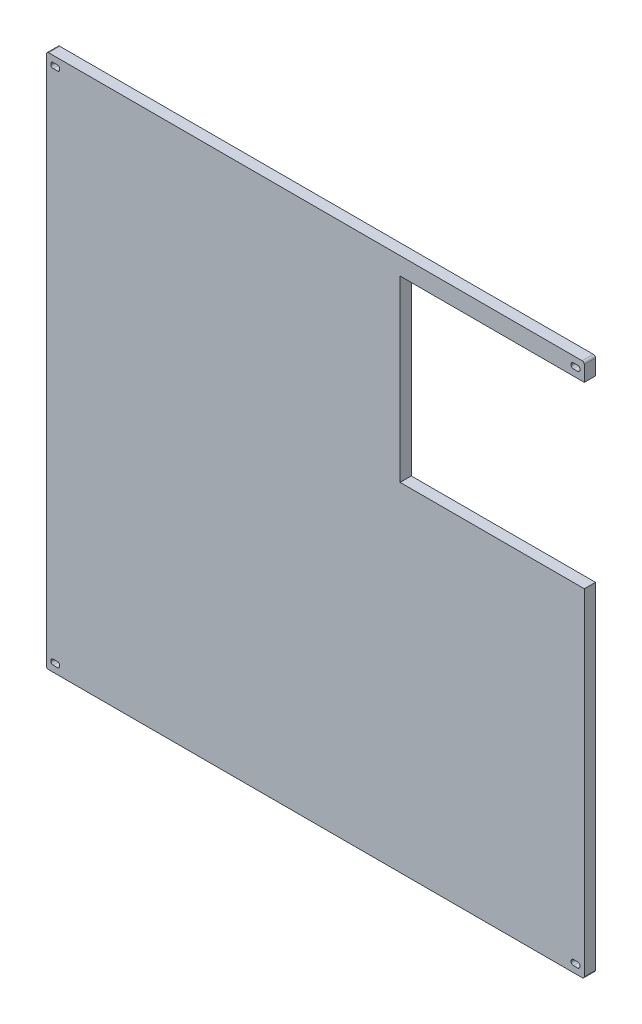
SolidWorks part; units mm, degrees
ref_plane "Front Plane" through (0, 0, 0) normal (0, 0, 1) x (1, 0, 0)
ref_plane "Top Plane" through (0, 0, 0) normal (0, 1, 0) x (1, 0, 0)
ref_plane "Right Plane" through (0, 0, 0) normal (1, 0, 0) x (0, 0, -1)
sketch "Sketch1" plane through (0, 0, 0) normal (0, 0, 1) x (1, 0, 0)
  line L0 (-5, 10.5) -> (-5, 9.5)
  line L1 (0, 0) -> (-611.632, 0)
  line L2 (0, 0) -> (0, 384.2809)
  line L3 (0, 607.568) -> (-611.632, 607.568)
  line L4 (-611.632, 0) -> (-611.632, 607.568)
  line L5 (0, 587.4809) -> (0, 607.568)
  line L6 (0, 587.4809) -> (-209.5191, 587.4809)
  line L8 (0, 384.2809) -> (-209.5191, 384.2809)
  line L9 (-209.5191, 587.4809) -> (-209.5191, 384.2809)
  line L10 (-7.5, 13) -> (-12.5, 13)
  line L11 (-15, 10.5) -> (-15, 9.5)
  line L12 (-7.5, 7) -> (-12.5, 7)
  line L13 (-10, 13) -> (-10, 7) construction
  line L14 (-15, 10) -> (-5, 10) construction
  line L15 (-596.63, 10.5) -> (-596.63, 9.5)
  line L16 (-599.13, 7) -> (-604.13, 7)
  line L17 (-606.63, 10.5) -> (-606.63, 9.5)
  line L18 (-599.13, 13) -> (-604.13, 13)
  line L19 (-596.63, 598.07) -> (-596.63, 597.07)
  line L20 (-599.13, 594.57) -> (-604.13, 594.57)
  line L21 (-606.63, 598.07) -> (-606.63, 597.07)
  line L22 (-599.13, 600.57) -> (-604.13, 600.57)
  line L23 (-5, 598.07) -> (-5, 597.07)
  line L24 (-7.5, 594.57) -> (-12.5, 594.57)
  line L25 (-15, 598.07) -> (-15, 597.07)
  line L26 (-7.5, 600.57) -> (-12.5, 600.57)
  line L27 (-209.5191, 641.3) -> (-209.5191, 384.2809) construction
  arc A0 (-5, 10.5) -> (-7.5, 13) centre (-7.5, 10.5) ccw
  arc A1 (-12.5, 13) -> (-15, 10.5) centre (-12.5, 10.5) ccw
  arc A2 (-5, 9.5) -> (-7.5, 7) centre (-7.5, 9.5) cw
  arc A3 (-15, 9.5) -> (-12.5, 7) centre (-12.5, 9.5) ccw
  arc A4 (-596.63, 9.5) -> (-599.13, 7) centre (-599.13, 9.5) cw
  arc A5 (-606.63, 9.5) -> (-604.13, 7) centre (-604.13, 9.5) ccw
  arc A6 (-604.13, 13) -> (-606.63, 10.5) centre (-604.13, 10.5) ccw
  arc A7 (-596.63, 10.5) -> (-599.13, 13) centre (-599.13, 10.5) ccw
  arc A8 (-596.63, 597.07) -> (-599.13, 594.57) centre (-599.13, 597.07) cw
  arc A9 (-606.63, 597.07) -> (-604.13, 594.57) centre (-604.13, 597.07) ccw
  arc A10 (-604.13, 600.57) -> (-606.63, 598.07) centre (-604.13, 598.07) ccw
  arc A11 (-596.63, 598.07) -> (-599.13, 600.57) centre (-599.13, 598.07) ccw
  arc A12 (-5, 597.07) -> (-7.5, 594.57) centre (-7.5, 597.07) cw
  arc A13 (-15, 597.07) -> (-12.5, 594.57) centre (-12.5, 597.07) ccw
  arc A14 (-12.5, 600.57) -> (-15, 598.07) centre (-12.5, 598.07) ccw
  arc A15 (-5, 598.07) -> (-7.5, 600.57) centre (-7.5, 598.07) ccw
  dimension "D4" = 2.5
  dimension "D1" = 611.632
  dimension "D2" = 607.568
  dimension "D3" = 6
  dimension "D5" = 10
  dimension "D6" = 10
  dimension "D7" = 2
  dimension "D8" = 2
  dimension "1000" = 10
  dimension "D9" = 5
  dimension "D10" = 6.998
  dimension "D11" = 5.002
  dimension "D12" = 384.2809
  dimension "D13" = 203.2
extrude "Boss-Extrude2" add sketch "Sketch1" along normal blind 12.7
fillet "Fillet2" radius 2.5 4 edges at (-611.632, 0, 6.35) (0, 0, 6.35) (-611.632, 607.568, 6.35) (0, 607.568, 6.35) tangent propagation no
